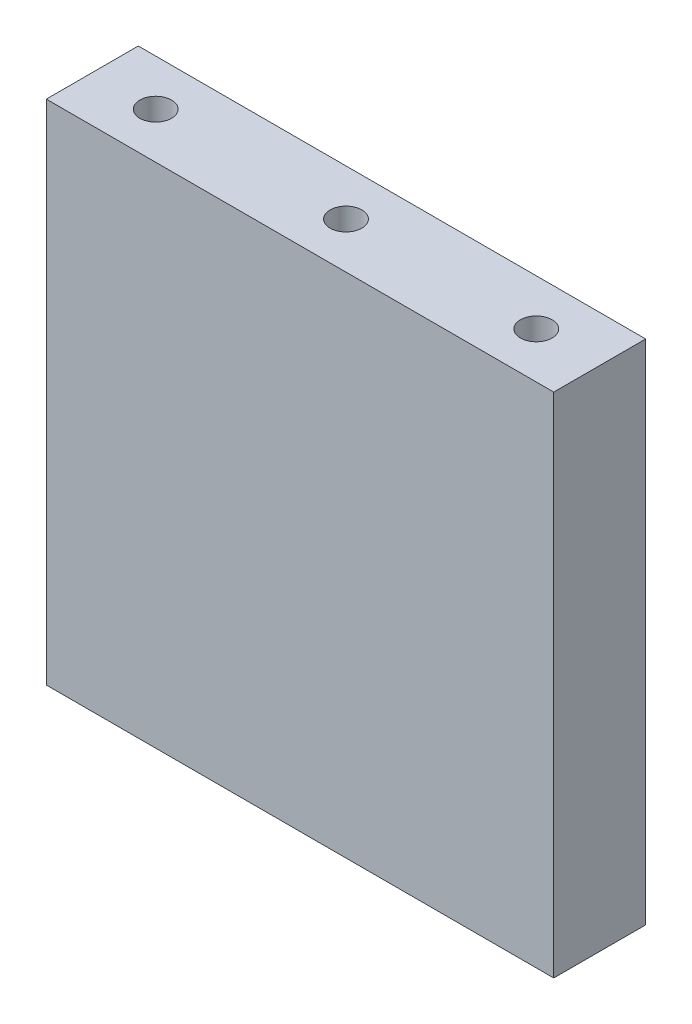
SolidWorks part; units mm, degrees
ref_plane "Front Plane" through (0, 0, 0) normal (0, 0, 1) x (1, 0, 0)
ref_plane "Top Plane" through (0, 0, 0) normal (0, 1, 0) x (1, 0, 0)
ref_plane "Right Plane" through (0, 0, 0) normal (1, 0, 0) x (0, 0, -1)
sketch "Sketch1" plane through (0, 0, 0) normal (0, 1, 0) x (1, 0, 0)
  line L1 (0, 0) -> (101.6, 0)
  line L2 (0, 0) -> (0, 18.415)
  line L3 (0, 18.415) -> (101.6, 18.415)
  line L4 (101.6, 0) -> (101.6, 18.415)
  dimension "D1" = 101.6
  dimension "D2" = 18.415
extrude "Boss-Extrude1" add sketch "Sketch1" along normal blind 101.6
sketch "Sketch2" plane through (0, 101.6, 0) normal (0, 1, 0) x (1, 0, 0)
  line L0 (0, 9.2075) -> (101.6, 9.2075) construction
  line L1 (0, 18.415) -> (0, 0) construction
  line L2 (101.6, 0) -> (101.6, 18.415) construction
  line L3 (50.8, 18.415) -> (50.8, 0) construction
  line L4 (101.6, 18.415) -> (0, 18.415) construction
  line L5 (0, 0) -> (101.6, 0) construction
  circle A0 centre (12.7, 9.2075) radius 3.175
  circle A1 centre (88.9, 9.2075) radius 3.175
  circle A2 centre (50.8, 9.2075) radius 3.175
  dimension "D1" = 6.35
  dimension "D2" = 76.2
  dimension "D3" = 6.35
  dimension "D4" = 6.35
  dimension "D5" = 12.7
extrude "Cut-Extrude1" cut sketch "Sketch2" against normal blind 12.7
sketch "Sketch3" plane through (0, 0, 0) normal (0, -1, 0) x (1, 0, 0)
  line L0 (0, -9.2075) -> (101.6, -9.2075) construction
  line L1 (0, -18.415) -> (0, 0) construction
  line L2 (101.6, 0) -> (101.6, -18.415) construction
  line L3 (50.8, 0) -> (50.8, -18.415) construction
  line L4 (0, 0) -> (101.6, 0) construction
  line L5 (101.6, -18.415) -> (0, -18.415) construction
  circle A0 centre (50.8, -9.2075) radius 3.175
  circle A1 centre (88.9, -9.2075) radius 3.175
  circle A2 centre (12.7, -9.2075) radius 3.175
  dimension "D1" = 6.35
  dimension "D2" = 76.2
  dimension "D3" = 6.35
  dimension "D5" = 6.35
  dimension "D4" = 12.7
extrude "Cut-Extrude2" cut sketch "Sketch3" against normal blind 12.7
